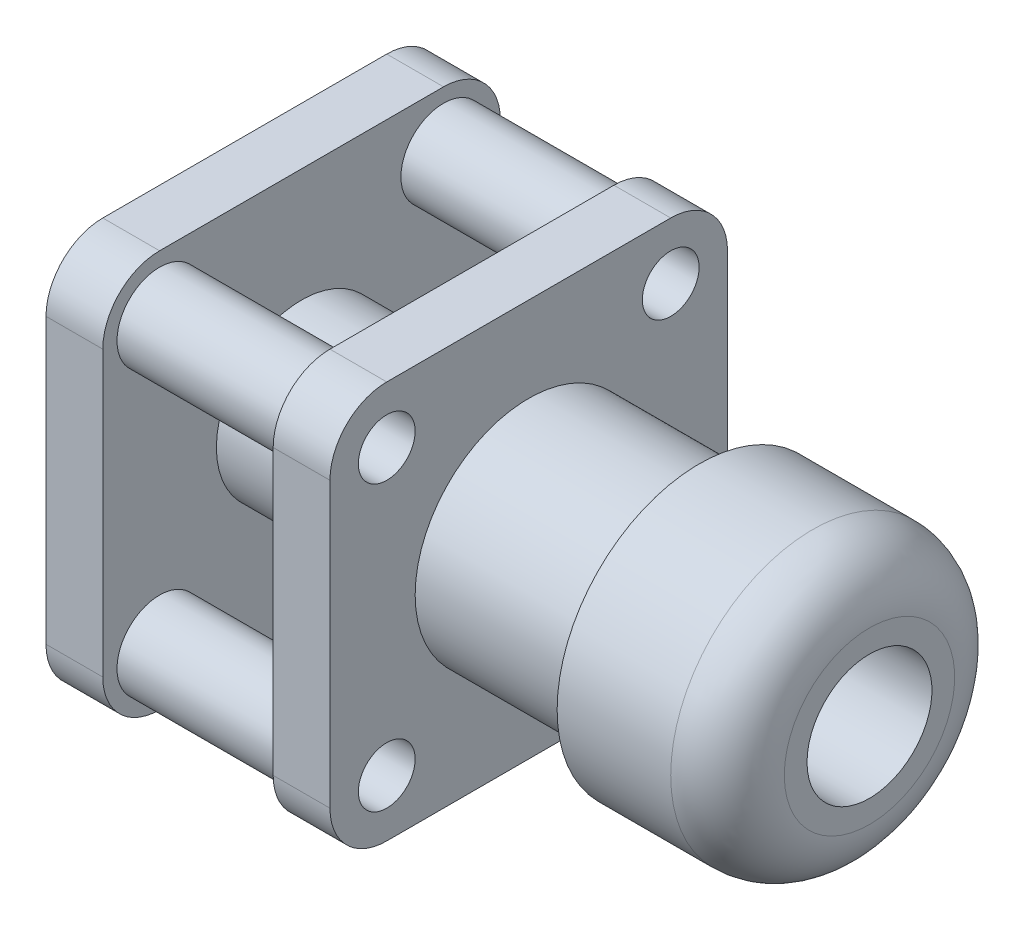
SolidWorks part; units mm, degrees
ref_plane "Спереди" through (0, 0, 0) normal (0, 0, 1) x (1, 0, 0)
ref_plane "Сверху" through (0, 0, 0) normal (0, 1, 0) x (1, 0, 0)
ref_plane "Справа" through (0, 0, 0) normal (1, 0, 0) x (0, 0, -1)
other "Configuration Table"
sketch "Эскиз1" plane through (0, 0, 0) normal (0, 0, 1) x (1, 0, 0)
  line L12 (0, 0) -> (182.4608, 0) construction
  line L13 (0, -1.7042) -> (0, -11) construction
  line L14 (0, -11) -> (0, -35)
  line L15 (0, -35) -> (10, -35)
  line L16 (10, -35) -> (10, -15)
  line L17 (10, -15) -> (40, -15)
  line L18 (40, -15) -> (40, -35)
  line L19 (40, -35) -> (50, -35)
  line L20 (50, -35) -> (50, -20)
  line L21 (50, -20) -> (80, -20)
  line L22 (80, -20) -> (80, -25)
  line L23 (80, -25) -> (100, -25)
  line L24 (110, -15) -> (110, -11)
  line L25 (110, -11) -> (110, 0) construction
  line L26 (0, -11) -> (110, -11)
  arc A0 (100, -25) -> (110, -15) centre (100, -15) ccw
  point P4 (0, 0)
  point P5 (0, 0)
  point P22 (110, -25)
  dimension "D12" = 10
  dimension "D1" = 11
  dimension "D2" = 35
  dimension "D3" = 10
  dimension "D4" = 15
  dimension "D5" = 30
  dimension "D6" = 10
  dimension "D7" = 30
  dimension "D8" = 30
  dimension "D9" = 25
  dimension "D10" = 20
  dimension "D11" = 35
revolve "Повернуть1" add sketch "Эскиз1" angle 360 about L12
sketch "Эскиз2" plane through (0, 0, 0) normal (-1, 0, 0) x (0, 0, 1)
  line L0 (0.1861, 0) -> (47.9577, 0) construction
  line L1 (-25, 35) -> (25, 35)
  line L2 (-35, 25) -> (-35, -25)
  line L3 (-25, -35) -> (25, -35)
  line L4 (35, 25) -> (35, -25)
  line L5 (-35, 35) -> (35, -35) construction
  line L6 (-35, -35) -> (35, 35) construction
  line L7 (0, 0) -> (0, 43.1048) construction
  circle A4 centre (25, 25) radius 7.5
  circle A5 centre (-25, 25) radius 7.5
  circle A6 centre (-25, -25) radius 7.5
  circle A7 centre (25, -25) radius 7.5
  arc A8 (-35, -25) -> (-25, -35) centre (-25, -25) ccw
  arc A9 (-25, 35) -> (-35, 25) centre (-25, 25) ccw
  arc A10 (25, 35) -> (35, 25) centre (25, 25) cw
  arc A11 (25, -35) -> (35, -25) centre (25, -25) ccw
  point P0 (0, 0)
  dimension "D7" = 15
  dimension "D8" = 15
  dimension "D9" = 15
  dimension "D10" = 15
  dimension "D11" = 25
  dimension "D12" = 25
  dimension "D15" = 10
  dimension "D1" = 70
  dimension "D2" = 70
  dimension "D3" = 25
  dimension "D4" = 25
  dimension "D5" = 25
  dimension "D6" = 25
  dimension "D13" = 25
  dimension "D14" = 25
extrude "Бобышка-Вытянуть1" add sketch "Эскиз2" against normal blind 10
extrude "Бобышка-Вытянуть2" add sketch "Эскиз2<3>" against normal blind 10 from offset 40 offset against normal yes
sketch "Эскиз2<3>" plane through (0, 0, 0) normal (-1, 0, 0) x (0, 0, 1) same geometry as "Эскиз2"
sketch "Эскиз3" plane through (0, 0, 0) normal (-1, 0, 0) x (0, 0, 1)
  line L0 (25, 35) -> (-25, 35) construction
  line L1 (35, -25) -> (35, 25) construction
  line L2 (-35, 25) -> (-35, -25) construction
  line L3 (-25, -35) -> (25, -35) construction
  circle A0 centre (-25, 25) radius 7.5
  circle A1 centre (25, 25) radius 7.5
  circle A2 centre (-25, -25) radius 7.5
  circle A3 centre (25, -25) radius 7.5
  circle A4 centre (0, 0) radius 11
  circle A5 centre (25, 25) radius 5
  circle A6 centre (25, -25) radius 5
  circle A7 centre (-25, -25) radius 5
  circle A8 centre (-25, 25) radius 5
  dimension "D9" = 15
  dimension "D10" = 15
  dimension "D11" = 15
  dimension "D12" = 15
  dimension "D13" = 22
  dimension "D14" = 10
  dimension "D15" = 10
  dimension "D16" = 10
  dimension "D17" = 10
  dimension "D1" = 10
  dimension "D2" = 10
  dimension "D3" = 10
  dimension "D4" = 10
  dimension "D5" = 10
  dimension "D6" = 10
  dimension "D7" = 10
  dimension "D8" = 10
extrude "Бобышка-Вытянуть3" add sketch "Эскиз3" against normal blind 50
sketch "Эскиз6" plane through (0, 0, 0) normal (-1, 0, 0) x (0, 0, 1)
  line L0 (25, 35) -> (-25, 35) construction
  line L1 (-35, 25) -> (-35, -25) construction
  line L2 (50, 0) -> (-50, 0) construction
  line L3 (0, -50) -> (0, 50) construction
  circle A3 centre (-25, 25) radius 5
  circle A4 centre (-25, -25) radius 5
  circle A5 centre (25, 25) radius 5
  circle A6 centre (25, -25) radius 5
  circle A7 centre (0, 0) radius 11
  dimension "D3" = 10
  dimension "D4" = 22
  dimension "D1" = 10
  dimension "D2" = 10
extrude "Вырез-Вытянуть2" cut sketch "Эскиз6" against normal through all both and the other way through all
